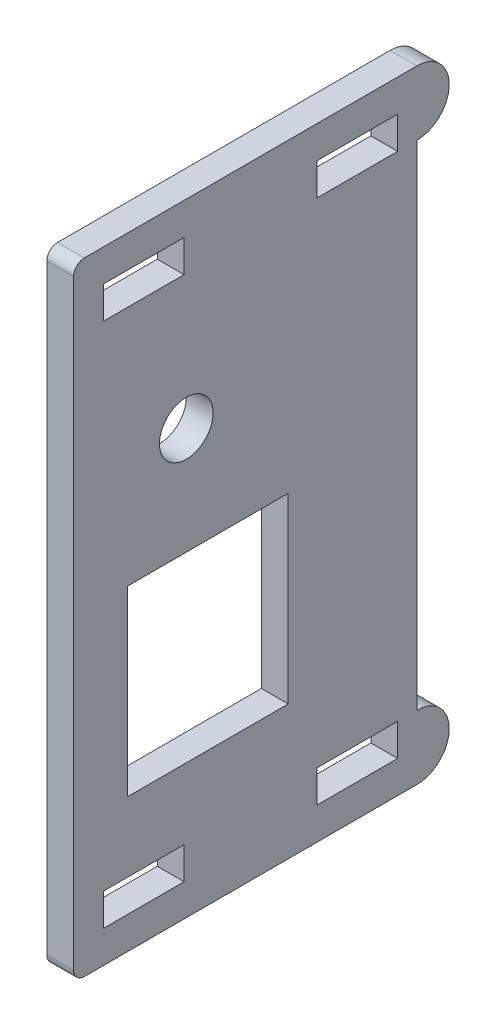
SolidWorks part; units mm, degrees
ref_plane "前视" through (0, 0, 0) normal (0, 0, 1) x (1, 0, 0)
ref_plane "上视" through (0, 0, 0) normal (0, 1, 0) x (1, 0, 0)
ref_plane "右视" through (0, 0, 0) normal (1, 0, 0) x (0, 0, -1)
sketch "草图2" plane through (0, 0, 0) normal (1, 0, 0) x (0, 0, -1)
  line L1 (-17.5, 29) -> (17.5, 29)
  line L2 (-17.5, 29) -> (-17.5, -29)
  line L3 (-17.5, -29) -> (17.5, -29)
  line L4 (17.5, 29) -> (17.5, -29)
  line L5 (-17.5, 29) -> (17.5, -29) construction
  line L6 (-17.5, -29) -> (17.5, 29) construction
  point P0 (0, 0)
  dimension "D1" = 58
  dimension "D2" = 35
extrude "凸台-拉伸1" add sketch "草图2" along normal blind 2.5
sketch "草图4" plane through (0, 0, 0) normal (-1, 0, 0) x (0, 0, 1)
  line L0 (-17.8855, 26) -> (19.6323, 26) construction
  line L1 (-17.5, 29) -> (17.5, 29) construction
  line L2 (-12.7, 26) -> (-5.2, 26)
  line L3 (-5.2, 26) -> (-5.2, 23)
  line L4 (-5.2, 23) -> (-12.7, 23)
  line L5 (-12.7, 23) -> (-12.7, 26)
  line L6 (-17.5, -29) -> (-17.5, 29) construction
  line L7 (7.2, 26) -> (14.7, 26)
  line L8 (14.7, 26) -> (14.7, 23)
  line L9 (14.7, 23) -> (7.2, 23)
  line L10 (7.2, 23) -> (7.2, 26)
  line L11 (17.5, 29) -> (17.5, -29) construction
  line L12 (0, 0) -> (-2.7087, 0) construction
  line L13 (-12.7, -23) -> (-12.7, -26)
  line L14 (7.2, -23) -> (7.2, -26)
  line L15 (-5.2, -26) -> (-5.2, -23)
  line L16 (14.7, -26) -> (14.7, -23)
  line L17 (14.7, -23) -> (7.2, -23)
  line L18 (7.2, -26) -> (14.7, -26)
  line L19 (-12.7, -26) -> (-5.2, -26)
  line L20 (-5.2, -23) -> (-12.7, -23)
  dimension "D1" = 3
  dimension "D2" = 4.8
  dimension "D3" = 3
  dimension "D4" = 7.5
  dimension "D5" = 7.5
  dimension "D6" = 3
  dimension "D7" = 2.8
extrude "切除-拉伸1" cut sketch "草图4" against normal through all
sketch "草图5" plane through (0, 0, 0) normal (-1, 0, 0) x (0, 0, 1)
  line L0 (-13.8103, 26) -> (-12.7631, 26) construction
  line L1 (-17.5, 29) -> (17.5, 29) construction
  line L2 (-14.5, 27.3502) -> (-14.5, 25.8843) construction
  line L3 (-17.5, -29) -> (-17.5, 29) construction
  line L4 (-11.0063, 0) -> (-20.4085, 0) construction
  line L5 (-14.5, 23) -> (-14.5, -23)
  line L6 (-14.5, 0) -> (-17.5, 0)
  line L7 (-17.5, -29) -> (-17.5, 29)
  line L8 (-14.5, 29) -> (-17.5, 29)
  line L9 (0, 0) -> (-4.681, 0) construction
  line L10 (-14.5, -29) -> (-17.5, -29)
  arc A0 (-14.5, 29) -> (-14.5, 23) centre (-14.5, 26) ccw
  arc A1 (-14.5, -29) -> (-14.5, -23) centre (-14.5, -26) cw
  line M9 (-17.5, 29) -> (-17.5, -29)
  line M10 (-17.5, -29) -> (17.5, -29)
  line M12 (17.5, 29) -> (-17.5, 29)
  dimension "D1" = 3
  dimension "D2" = 3
extrude "切除-拉伸2" cut sketch "草图5" against normal through all contours A0 M12 M9 | A0 L7 L6 L5 | A1 L5 L6 M9 | A1 L7 M10 | L7 L8 A0 L5 A1 L10 region at (0, -28.3299, -16.8299) region at (0, 28.3299, -16.8299) region at (0, 11.8314, -16.0226) region at (0, -11.8314, -16.0226)
sketch "草图7" plane through (0, 0, 0) normal (-1, 0, 0) x (0, 0, 1)
  line L0 (-12.7, -26) -> (-5.2, -26) construction
  line L1 (-2.5, 0.5) -> (12.5, 0.5)
  line L2 (-2.5, 0.5) -> (-2.5, -16.5)
  line L3 (-2.5, -16.5) -> (12.5, -16.5)
  line L4 (12.5, 0.5) -> (12.5, -16.5)
  line L5 (-14.5, 23) -> (-14.5, -23) construction
  line L6 (0, 0) -> (-3.3542, 0) construction
  circle A0 centre (7, 10.5) radius 2.5
  dimension "D7" = 5
  dimension "D1" = 9.5
  dimension "D2" = 17
  dimension "D3" = 15
  dimension "D4" = 12
  dimension "D5" = 10
  dimension "D6" = 21.5
extrude "切除-拉伸3" cut sketch "草图7" against normal through all
fillet "圆角1" radius 1 2 edges at (1.25, -29, 17.5) (1.25, 29, 17.5)
